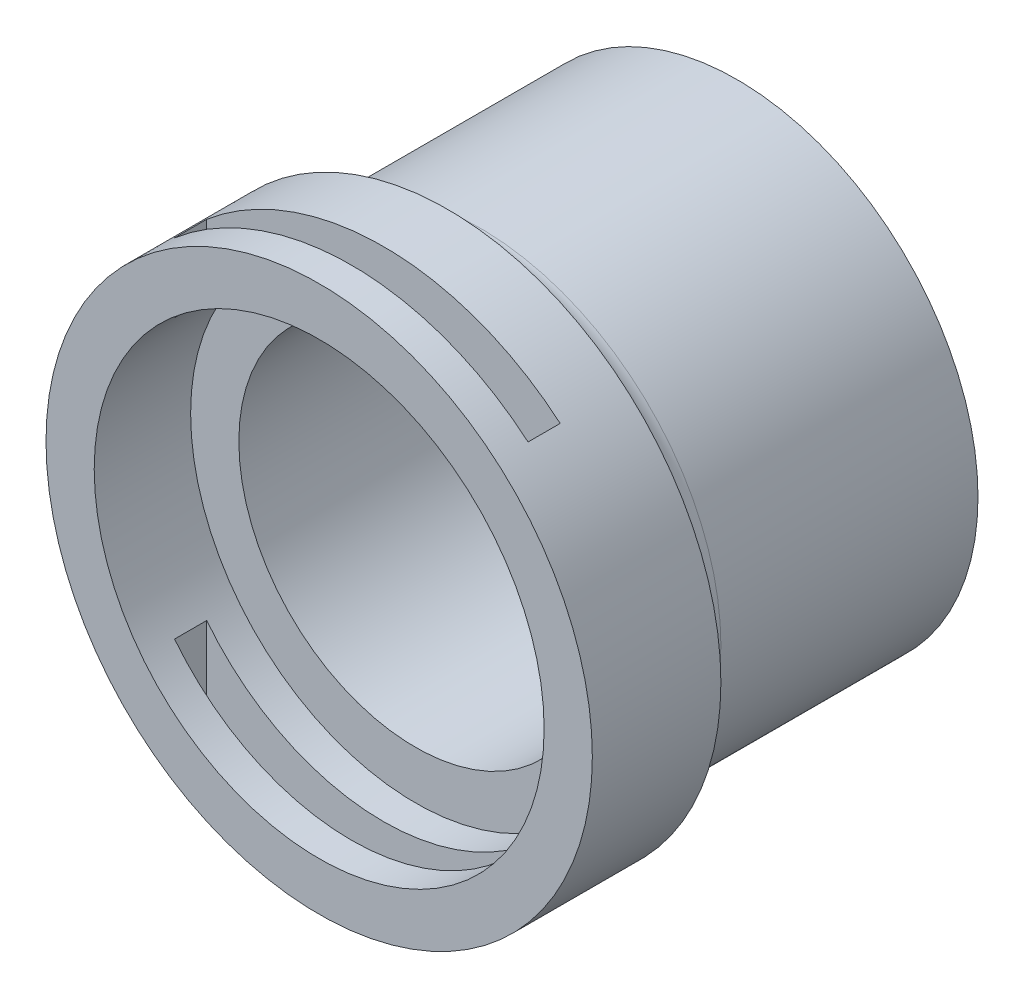
SolidWorks part; units mm, degrees
material "ABS"
ref_plane "Front Plane" through (0, 0, 0) normal (0, 0, 1) x (1, 0, 0)
ref_plane "Top Plane" through (0, 0, 0) normal (0, 1, 0) x (1, 0, 0)
ref_plane "Right Plane" through (0, 0, 0) normal (1, 0, 0) x (0, 0, -1)
sketch "Sketch1" plane through (0, 0, 0) normal (0, 0, 1) x (1, 0, 0)
  circle A0 centre (0, 0) radius 15
  dimension "D1" = 30
extrude "Boss-Extrude5" add sketch "Sketch1" along normal blind 26 contours A0
sketch "Sketch3" plane through (0, 0, 26) normal (0, 0, 1) x (1, 0, 0)
  circle A0 centre (0, 0) radius 5.625
  dimension "D1" = 11.25
extrude "Cut-Extrude2" cut sketch "Sketch3" against normal through all
sketch "Sketch4" plane through (0, 0, 26) normal (0, 0, 1) x (1, 0, 0)
  circle A0 centre (0, 0) radius 11
  circle A2 centre (0, 0) radius 15 construction
  dimension "D1" = 22
  dimension "D2" = 4
extrude "Cut-Extrude3" cut sketch "Sketch4" against normal blind 20 and the other way blind 28
sketch "Sketch7" plane through (0, 0, 0) normal (0, 0, 1) x (1, 0, 0)
  circle A1 centre (0, 0) radius 11
  circle A2 centre (0, 0) radius 9
  dimension "D1" = 18
  dimension "D2" = 22
extrude "Cut-Extrude6" cut sketch "Sketch7" against normal blind 2 from surface starting at face at (11, 0, 6)
sketch "Sketch12" plane through (0, 0, 0) normal (0, 0, 1) x (1, 0, 0)
  circle A0 centre (0, 0) radius 17
  dimension "D1" = 34
extrude "Boss-Extrude8" add sketch "Sketch12" along normal up to surface (26 mm away) and the other way blind 2 from offset 20 up to face at (15, 0, 26)
sketch "Sketch13" plane through (0, 0, 0) normal (0, 0, 1) x (1, 0, 0)
  circle A0 centre (0, 0) radius 11
extrude "Cut-Extrude10" cut sketch "Sketch13" along normal through all from surface starting at face at (11, 0, 18)
fillet "Fillet2" radius 2 1 edges at (15, 0, 18)
sketch "Sketch14" plane through (0, 0, 0) normal (0, 0, 1) x (1, 0, 0)
  circle A0 centre (0, 0) radius 14
  dimension "D1" = 28
extrude "Cut-Extrude11" cut sketch "Sketch14" against normal blind 6 from surface starting at face at (17, 0, 26)
sketch "Sketch15" plane through (0, 0, 0) normal (0, 0, 1) x (1, 0, 0)
  circle A0 centre (0, 10) radius 0.5
  circle A1 centre (0, 0) radius 11 construction
  circle A3 centre (0, -10) radius 0.5
  circle A4 centre (10, 0) radius 0.5
  circle A5 centre (-10, 0) radius 0.5
  dimension "D1" = 10
extrude "Cut-Extrude14" cut sketch "Sketch15" along normal through all contours A3 | A4 | A0 | A5
sketch "Sketch18" plane through (0, 0, 0) normal (0, 1, 0) x (1, 0, 0)
  line L1 (11, -22) -> (-11, -22)
  line L2 (11, -22) -> (11, -24)
  line L3 (11, -24) -> (-11, -24)
  line L4 (-11, -22) -> (-11, -24)
  line L5 (11, -22) -> (-11, -24) construction
  line L6 (11, -24) -> (-11, -22) construction
  point P0 (0, -23)
extrude "Cut-Extrude15" cut sketch "Sketch18" against normal through all and the other way through all
